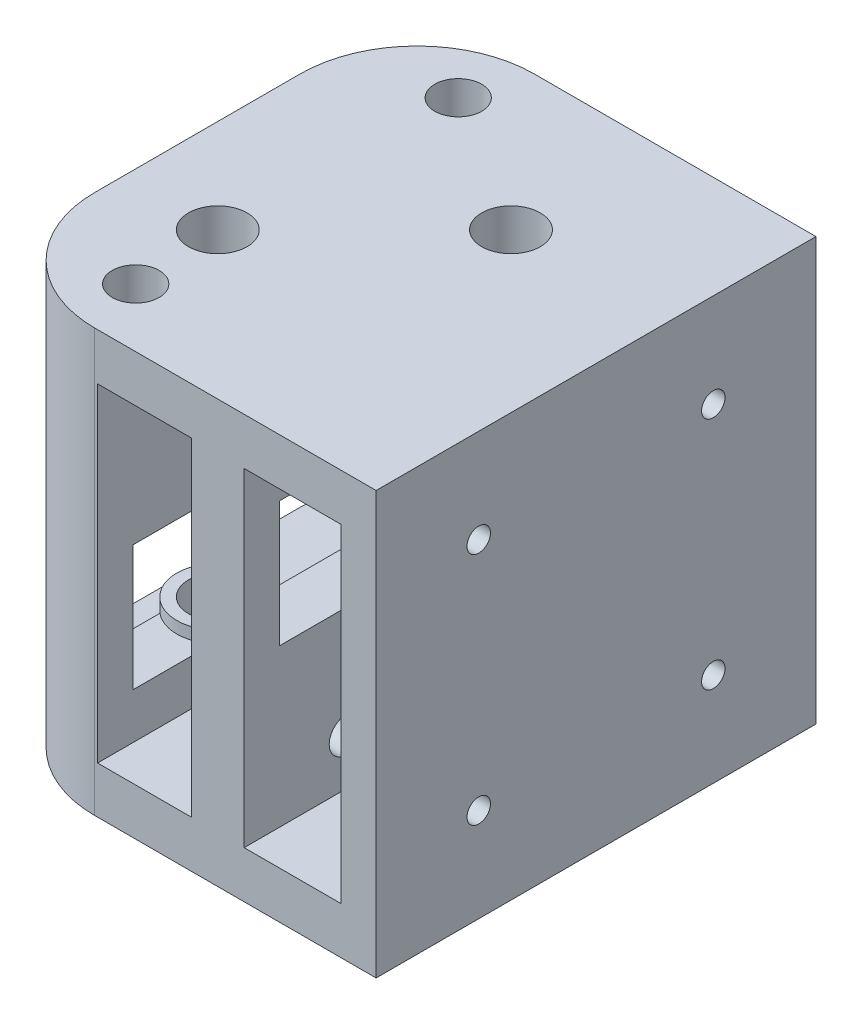
SolidWorks part; units mm, degrees
ref_plane "Front Plane" through (0, 0, 0) normal (0, 0, 1) x (1, 0, 0)
ref_plane "Top Plane" through (0, 0, 0) normal (0, 1, 0) x (1, 0, 0)
ref_plane "Right Plane" through (0, 0, 0) normal (1, 0, 0) x (0, 0, -1)
sketch "Top-Sketch1" plane through (0, 0, 0) normal (0, 1, 0) x (1, 0, 0)
  line L1 (0, 0) -> (34, 0)
  line L2 (0, 0) -> (0, 37.5)
  line L3 (0, 37.5) -> (34, 37.5)
  line L4 (34, 0) -> (34, 37.5)
  circle A0 centre (8.5, 32.5) radius 2
  circle A1 centre (8.5, 5) radius 2
  circle A2 centre (8, 12.5) radius 2.5
  circle A3 centre (20.5, 25) radius 2.5
  dimension "D3" = 5
  dimension "D5" = 4
  dimension "D1" = 13.5
  dimension "D2" = 12.5
  dimension "D4" = 12.5
  dimension "D6" = 8
  dimension "D8" = 12.5
  dimension "D9" = 5
  dimension "D10" = 5
  dimension "D11" = 37.5
  dimension "D12" = 12.5
  dimension "D7" = 25.5
extrude "Boss-Extrude4" add sketch "Top-Sketch1" along normal blind 4
sketch "TopRightRiser" plane through (0, 0, 0) normal (0, -1, 0) x (1, 0, 0)
  line L0 (5.75, -9.819) -> (5.75, 0)
  line L1 (0, 0) -> (34, 0) construction
  line L2 (5.75, 0) -> (10.25, 0)
  line L3 (10.25, 0) -> (10.25, -9.819)
  arc A0 (5.75, -9.819) -> (10.25, -9.819) centre (8, -12.5) ccw
  circle A1 centre (8, -12.5) radius 2.5 construction
  circle A2 centre (8, -12.5) radius 2.5
  point P13 (8, 0)
  dimension "D1" = 7
  dimension "D2" = 4.5
extrude "TopRightRiserBoss-Extrude5" add sketch "TopRightRiser" along normal blind 14.4
sketch "TopLeft" plane through (0, 0, 0) normal (0, -1, 0) x (1, 0, 0)
  line L0 (18.25, -22.319) -> (18.25, 0)
  line L1 (10.25, 0) -> (34, 0) construction
  line L2 (18.25, 0) -> (22.75, 0)
  line L3 (22.75, 0) -> (22.75, -22.319)
  line L4 (10.25, 0) -> (5.75, 0) construction
  circle A0 centre (20.5, -25) radius 2.5
  circle A1 centre (20.5, -25) radius 2.5 construction
  arc A2 (18.25, -22.319) -> (22.75, -22.319) centre (20.5, -25) ccw
  arc A3 (5.75, -9.819) -> (10.25, -9.819) centre (8, -12.5) ccw construction
  point P16 (20.5, 0)
extrude "TopLeftBoss-Extrude6" add sketch "TopLeft" along normal blind 4.9
sketch "MidWall" plane through (0, 0, 0) normal (0, -1, 0) x (-1, 0, 0)
  line L0 (-10.25, 9.819) -> (-10.25, 5.9682) construction
  line L1 (0, 3) -> (-10.25, 3)
  line L2 (0, 3) -> (0, 0)
  line L3 (0, 0) -> (-10.25, 0)
  line L4 (-10.25, 3) -> (-10.25, 0)
  line L5 (0, 37.5) -> (0, 0) construction
  line L6 (-10.25, 0) -> (-5.75, 0) construction
  line L7 (-18.25, 0) -> (-18.25, 22.319) construction
  line L8 (-18.25, 0) -> (-22.75, 0)
  line L9 (-18.25, 0) -> (-18.25, 3)
  line L10 (-18.25, 3) -> (-22.75, 3)
  line L11 (-22.75, 0) -> (-22.75, 3)
  line L12 (-22.75, 22.319) -> (-22.75, 0) construction
  line L13 (-10.25, 0) -> (-18.25, 0) construction
  line L14 (-22.75, 0) -> (-34, 0) construction
  line L15 (-31, 0) -> (-34, 0)
  line L16 (-31, 0) -> (-31, 37.5)
  line L17 (-31, 37.5) -> (-34, 37.5)
  line L18 (-34, 0) -> (-34, 37.5)
  line L19 (-34, 37.5) -> (0, 37.5) construction
  line L20 (-34, 0) -> (-34, 37.5) construction
  dimension "D1" = 3
extrude "MidWallBoss-Extrude7" add sketch "MidWall" along normal blind 28
sketch "Bottom" plane through (0, -28, 0) normal (0, -1, 0) x (1, 0, 0)
  line L0 (0, 0) -> (34, 0) construction
  line L1 (0, 0) -> (34, 0)
  line L2 (0, 0) -> (0, -37.5)
  line L3 (0, -37.5) -> (34, -37.5)
  line L4 (34, 0) -> (34, -37.5)
  line L5 (34, 0) -> (34, -37.5) construction
  line L6 (0, -37.5) -> (0, 0) construction
extrude "BottomBoss-Extrude8" add sketch "Bottom" along normal blind 4
sketch "LowerRight" plane through (0, -28, 0) normal (0, 1, 0) x (1, 0, 0)
  line L0 (5.75, 9.819) -> (5.75, 3)
  line L1 (5.75, 3) -> (10.25, 3)
  line L2 (10.25, 3) -> (10.25, 9.819)
  line L6 (10.25, 9.819) -> (10.25, 3) construction
  line L7 (5.75, 3) -> (5.75, 9.819) construction
  line L8 (10.25, 3) -> (5.75, 3) construction
  circle A0 centre (8, 12.5) radius 2.5
  arc A1 (10.25, 9.819) -> (5.75, 9.819) centre (8, 12.5) ccw
  circle A2 centre (8, 12.5) radius 2.5 construction
  arc A3 (10.25, 9.819) -> (5.75, 9.819) centre (8, 12.5) ccw construction
extrude "LowerRightBoss-Extrude10" add sketch "LowerRight" along normal blind 4.9
sketch "LowerLeft" plane through (0, -28, 0) normal (0, 1, 0) x (1, 0, 0)
  line L1 (18.25, 0) -> (22.75, 0)
  line L5 (0, 0) -> (34, 0) construction
  line L6 (18.25, 22.319) -> (18.25, 0)
  line L7 (22.75, 22.319) -> (22.75, 0)
  circle A0 centre (20.5, 25) radius 2.5
  arc A1 (22.75, 22.319) -> (18.25, 22.319) centre (20.5, 25) ccw
  circle A2 centre (20.5, 25) radius 2.5 construction
  arc A3 (22.75, 22.319) -> (18.25, 22.319) centre (20.5, 25) ccw construction
  point P3 (20.5, 0)
  dimension "D1" = 4.5
extrude "LowerLeftBoss-Extrude9" add sketch "LowerLeft" along normal blind 14.4
fillet "Fillet1" radius 10 3 edges at (0, -14, 0) (0, -30, -37.5) (0, 2, -37.5)
sketch "LinearRailMountingHoles-Sketch10" plane through (34, 0, 0) normal (1, 0, 0) x (0, 0, -1)
  line L0 (0, 4) -> (37.5, 4) construction
  line L1 (37.5, 4) -> (37.5, -32) construction
  line L3 (37.5, -32) -> (0, -32) construction
  line L4 (0, 4) -> (0, -32) construction
  circle A0 centre (8.75, -4) radius 1
  circle A1 centre (8.75, -24) radius 1
  circle A2 centre (28.75, -24) radius 1
  circle A3 centre (28.75, -4) radius 1
  dimension "D7" = 2
  dimension "D1" = 8
  dimension "D2" = 20
  dimension "D3" = 20
  dimension "D4" = 8.75
  dimension "D5" = 8
  dimension "D6" = 8.75
extrude "LinearRailMountingHolesCut-Extrude1" cut sketch "LinearRailMountingHoles-Sketch10" against normal blind 3
sketch "TopRightInset-Sketch1" plane through (0, -14.4, 0) normal (0, -1, 0) x (1, 0, 0)
  line L0 (5.75, -9.819) -> (5.75, -3)
  line L1 (5.75, -3) -> (10.25, -3)
  line L2 (10.25, -3) -> (10.25, -9.819)
  line L3 (5.75, -9.819) -> (5.75, -3) construction
  line L4 (5.75, -3) -> (10.25, -3) construction
  line L5 (10.25, -3) -> (10.25, -9.819) construction
  arc A0 (10.25, -9.819) -> (5.75, -9.819) centre (8, -12.5) ccw
  arc A1 (5.75, -9.819) -> (10.25, -9.819) centre (8, -12.5) ccw construction
extrude "TopRightInset-Cut-Extrude1" cut sketch "TopRightInset-Sketch1" against normal blind 1
sketch "TopLeftInset-Sketch2" plane through (0, -4.9, 0) normal (0, -1, 0) x (1, 0, 0)
  line L0 (18.25, -22.319) -> (18.25, -3)
  line L1 (18.25, -3) -> (22.75, -3)
  line L2 (22.75, -3) -> (22.75, -22.319)
  line L3 (22.75, -3) -> (18.25, -3) construction
  line L4 (22.75, -22.319) -> (22.75, -3) construction
  line L5 (18.25, -22.319) -> (18.25, -3) construction
  arc A0 (22.75, -22.319) -> (18.25, -22.319) centre (20.5, -25) ccw
  arc A1 (18.25, -22.319) -> (22.75, -22.319) centre (20.5, -25) ccw construction
extrude "TopLeftInset-Cut-Extrude2" cut sketch "TopLeftInset-Sketch2" against normal blind 1
sketch "LowerLeftInset-Sketch3" plane through (0, -13.6, 0) normal (0, 1, 0) x (1, 0, 0)
  line L0 (18.25, 22.319) -> (18.25, 3)
  line L1 (18.25, 3) -> (22.75, 3)
  line L2 (22.75, 3) -> (22.75, 22.319)
  line L3 (22.75, 3) -> (18.25, 3) construction
  line L4 (18.25, 22.319) -> (18.25, 3) construction
  line L5 (22.75, 3) -> (22.75, 22.319) construction
  arc A0 (18.25, 22.319) -> (22.75, 22.319) centre (20.5, 25) ccw
  arc A1 (22.75, 22.319) -> (18.25, 22.319) centre (20.5, 25) ccw construction
extrude "LowerLeftInset-Cut-Extrude3" cut sketch "LowerLeftInset-Sketch3" against normal blind 1
sketch "LowerRightInset-Sketch4" plane through (0, -23.1, 0) normal (0, 1, 0) x (1, 0, 0)
  line L0 (5.75, 9.819) -> (5.75, 3)
  line L1 (5.75, 3) -> (10.25, 3)
  line L2 (10.25, 3) -> (10.25, 9.819)
  line L3 (10.25, 3) -> (5.75, 3) construction
  line L4 (5.75, 3) -> (5.75, 9.819) construction
  line L5 (10.25, 9.819) -> (10.25, 3) construction
  arc A0 (5.75, 9.819) -> (10.25, 9.819) centre (8, 12.5) ccw
  arc A1 (10.25, 9.819) -> (5.75, 9.819) centre (8, 12.5) ccw construction
extrude "LowerRightInsetCut-Extrude4" cut sketch "LowerRightInset-Sketch4" against normal blind 1
sketch "PushPinHoleSketch1" plane through (0, -32, 0) normal (0, -1, 0) x (1, 0, 0)
  circle A0 centre (20.5, -25) radius 1
  circle A1 centre (8, -12.5) radius 1
  circle A2 centre (8, -12.5) radius 2.5 construction
  circle A3 centre (20.5, -25) radius 2.5 construction
  dimension "D1" = 2
extrude "PushPinHoleCut-Extrude5" cut sketch "PushPinHoleSketch1" against normal through all
sketch "TopRightMountHoleAccessSketch2" plane through (5.75, 0, 0) normal (-1, 0, 0) x (0, 0, 1)
  circle A0 centre (-8.75, -4) radius 1.5
  dimension "D1" = 3
extrude "TopRightMountHoleAccessCut-Extrude2" cut sketch "TopRightMountHoleAccessSketch2" against normal blind 20 and the other way through all
sketch "BottomRightMountHoleAccessSketch3" plane through (18.25, 0, 0) normal (-1, 0, 0) x (0, 0, 1)
  circle A0 centre (-8.75, -24) radius 1.5
  arc A1 (-9.819, -5.0522) -> (-9.819, -2.9478) centre (-8.75, -4) ccw construction
extrude "BottomRightMountHoleAccessCut-Extrude3" cut sketch "BottomRightMountHoleAccessSketch3" against normal blind 5
equation "\"GABDepth\"= \"GABDistanceFromBackToFirstPulley\" + \"GABPulleyDDistanceBetween\" + \"GABDistanceFromPulleyToFront\""
equation "\"GABWidth\"= \"StandardWallThickness\" + \"GABDistanceFromLSideToPulley\" + \"GABPulleyWDistanceBetween\" + \"GABDistanceFromPulleyToRSide\""
equation "\"GABLowerHeight\"= 4mm"
equation "\"GABUpperHeight\"= 4mm"
equation "\"GABMidWallHeight\"= 28mm'Must equal 28 or changes alignment"
equation "\"StandardWallThickness\"= 3mm"
equation "\"GABMidShortRiserHeight\"= \"GABMidWallHeight\" / 2 - \"20TGT2PulleyWidth\"'Equals 5.3"
equation "\"LinearGBMountHolesXDistance\"= 20mm'Spec"
equation "\"GABHeight\"= \"GABLowerHeight\" + \"GABMidWallHeight\" + \"GABUpperHeight\""
equation "\"GBMountingHoleDiameter\"= 2mm"
equation "\"GABMidLongRiserHeight\"= \"GABMidWallHeight\" - \"GABMidShortRiserHeight\" - \"20TGT2PulleyWidth\"'Equals 14"
equation "\"GABLRClampHoleOffsetFromSide\"= 5mm"
equation "\"GABDistanceFromBackToFirstPulley\"= 13.5mm"
equation "\"GABPulleyDDistanceBetween\"= 12.5mm'From the100"
equation "\"GABPulleyWDistanceBetween\"= 14.5mm'From the100"
equation "\"GABDistanceFromPulleyToFront\"= 8mm"
equation "\"GABDistanceFromLSideToPulley\"= 9.5mm + \"StandardWallThickness\""
equation "\"GABDistanceFromPulleyToRSide\"= 7.5mm"
equation "\"GABDistanceToFrontClampHoles\"= 8.5mm"
equation "\"SteelShaft5mmHoleDiameter\"= 5mm"
equation "\"20TGT2PulleyWidth\"= 8.7mm'The STL of the Pulley in the diagram is a bit larger"
equation "\"7mmx1mmSpacerDiameter\"= 7mm"
equation "\"7mmx1mmSpacerHeight\"= 1mm"
equation "\"GABRiserBossOffset\" = 0.4mm'Aligns Pulleys inside edges to be 2.5mm (.5mm apart top to bottom)"
equation "\"D1@Top-Sketch1\" = \"GABDistanceFromBackToFirstPulley\""
equation "\"D2@Top-Sketch1\" = \"GABPulleyDDistanceBetween\""
equation "\"D3@Top-Sketch1\" = \"SteelShaft5mmHoleDiameter\""
equation "\"D4@Top-Sketch1\" = \"GABPulleyDDistanceBetween\""
equation "\"D6@Top-Sketch1\" = \"GABDistanceFromPulleyToFront\""
equation "\"D8@Top-Sketch1\" = \"GABDistanceFromLSideToPulley\""
equation "\"D9@Top-Sketch1\" = \"GABLRClampHoleOffsetFromSide\""
equation "\"D10@Top-Sketch1\" = \"GABLRClampHoleOffsetFromSide\""
equation "\"D11@Top-Sketch1\" = \"GABWidth\""
equation "\"D1@Boss-Extrude4\"=\"GABUpperHeight\""
equation "\"D1@TopRightRiserBoss-Extrude5\" = \"GABMidLongRiserHeight\" + \"GABRiserBossOffset\""
equation "\"D1@TopLeftBoss-Extrude6\" = \"GABMidShortRiserHeight\" - \"GABRiserBossOffset\""
equation "\"D1@MidWall\" = \"StandardWallThickness\""
equation "\"D1@MidWallBoss-Extrude7\" = \"GABMidWallHeight\""
equation "\"D1@BottomBoss-Extrude8\" = \"GABLowerHeight\""
equation "\"D1@LowerLeftBoss-Extrude9\" = \"GABMidLongRiserHeight\" + \"GABRiserBossOffset\""
equation "\"D1@LowerRightBoss-Extrude10\" = \"GABMidShortRiserHeight\" - \"GABRiserBossOffset\""
equation "\"D1@LinearRailMountingHoles-Sketch10\" =  ( \"GABHeight\" - \"LinearGBMountHolesXDistance\" )  / 2"
equation "\"D2@LinearRailMountingHoles-Sketch10\"=\"LinearGBMountHolesYDistance\""
equation "\"D3@LinearRailMountingHoles-Sketch10\" = \"LinearGBMountHolesXDistance\""
equation "\"D4@LinearRailMountingHoles-Sketch10\" =  ( \"GABWidth\" - \"LinearGBMountHolesXDistance\" )  / 2"
equation "\"D7@LinearRailMountingHoles-Sketch10\" = \"GBMountingHoleDiameter\""
equation "\"D1@LinearRailMountingHolesCut-Extrude1\" = \"StandardWallThickness\""
equation "\"D1@TopRightInset-Cut-Extrude1\" = \"7mmx1mmSpacerHeight\""
equation "\"D1@TopLeftInset-Cut-Extrude2\" = \"7mmx1mmSpacerHeight\""
equation "\"D1@LowerRightInsetCut-Extrude4\" = \"7mmx1mmSpacerHeight\""
equation "\"D1@TopRightRiser\"=\"7mmx1mmSpacerDiameter\""
equation "\"D7@Top-Sketch1\"=\"GABDepth\" - \"GABDistanceToFrontClampHoles\""
equation "\"LinearGBMountHolesYDistance\"= 20mm'Spec"
equation "\"D1@PushPinHoleSketch1\" = \"StealPinPushHoleDiameter\""
equation "\"StealPinPushHoleDiameter\"= 2mm"
equation "\"M3HeatInsertHoleDiameter\"= 4mm'Spec"
equation "\"D5@Top-Sketch1\"=\"M3HeatInsertHoleDiameter\""
